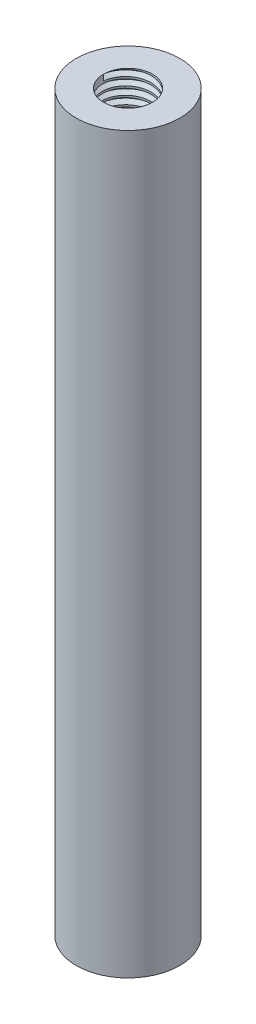
SolidWorks part; units mm, degrees
ref_plane "Front Plane" through (0, 0, 0) normal (0, 0, 1) x (1, 0, 0)
ref_plane "Top Plane" through (0, 0, 0) normal (0, 1, 0) x (1, 0, 0)
ref_plane "Right Plane" through (0, 0, 0) normal (1, 0, 0) x (0, 0, -1)
sketch "Sketch1" plane through (0, 0, 0) normal (0, 1, 0) x (1, 0, 0)
  circle A0 centre (0, 0) radius 6.35
extrude "Boss-Extrude1" add sketch "Sketch1" along normal blind 90
sketch "Sketch2" plane through (0, 90, 0) normal (0, 1, 0) x (1, 0, 0)
  point P0 (0, 0)
sketch "Sketch3" plane through (0, 0, 0) normal (0, -1, 0) x (-1, 0, 0)
  point P0 (0, 0)
hole_wizard "Tap Drill for M7x1.0 Tap1" positions "Sketch4" profile "Sketch5" hole size "M7x1.0" standard "ANSI Metric"
sketch "Sketch4" plane through (0, 90, 0) normal (0, 1, 0) x (1, 0, 0)
  point P0 (0, 0)
sketch "Sketch5" plane through (0, 90, 0) normal (1, 0, 0) x (0, 0, 1)
  line L0 (0, 0) -> (0, 27.2026)
  line L1 (0, 27.2026) -> (3, 25.4)
  line L2 (3, 25.4) -> (3, 0)
  line L5 (3, 0) -> (0, 0)
  line L10 (0, 27.2026) -> (-3, 25.4) construction
  line L11 (0, -6.35) -> (0, 107.95) construction
  dimension "Hole Dia." = 6
  dimension "Hole Depth" = 25.4
  dimension "Drill Angle" = 118
thread "Thread1" pitch 1 start angle 0, offset 0, length 0, pitch 1, diameter 6
ref_plane "Plane1" through (-3, 90, 0) normal (0, 0, 1) x (-1, 0, 0)
sketch "Thread Profile1" plane through (-3, 90, 0) normal (0, 0, 1) x (-1, 0, 0)
  line L0 (0, 0) -> (0, 1) construction
  line L1 (0, 0) -> (0.5413, 0.3125)
  line L2 (0.5413, 0.3125) -> (0.5413, 0.4375)
  line L3 (0.5413, 0.4375) -> (0, 0.75)
  line L4 (0.5413, 0.375) -> (0, 0.375) construction
  line L11 (0, 0) -> (0, 0.75)
  point P2 (0, 0)
  dimension "Pitch" = 1
  dimension "Profile_Angle" = 60
  dimension "Profile_Land" = 0.125
  dimension "Profile_Height" = 0.5413
hole_wizard "Tap Drill for 1/4-20 Tap1" positions "Sketch10" profile "Sketch11" hole size "1/4-20" standard "ANSI Inch"
sketch "Sketch10" plane through (0, 0, 0) normal (0, -1, 0) x (-1, 0, 0)
  point P0 (0, 0)
sketch "Sketch11" plane through (0, 0, 0) normal (1, 0, 0) x (0, 0, -1)
  line L0 (0, 0) -> (0, 26.9338)
  line L1 (0, 26.9338) -> (2.5527, 25.4)
  line L2 (2.5527, 25.4) -> (2.5527, 0)
  line L5 (2.5527, 0) -> (0, 0)
  line L10 (0, 26.9338) -> (-2.5527, 25.4) construction
  line L11 (0, -6.35) -> (0, 107.95) construction
  dimension "Hole Dia." = 5.1054
  dimension "Hole Depth" = 25.4
  dimension "Drill Angle" = 118
thread "Thread2" pitch 1.27 profile "Thread Profile2" start angle 0, offset 0, length 0, pitch 1.27, diameter 5.1054
ref_plane "Plane2" through (2.5527, 0, 0) normal (0, 0, 1) x (1, 0, 0)
sketch "Thread Profile2" plane through (2.5527, 0, 0) normal (0, 0, 1) x (1, 0, 0)
  line L0 (0, 0) -> (0, 1.27) construction
  line L1 (0, 0) -> (0.6874, 0.3969)
  line L2 (0.6874, 0.3969) -> (0.6874, 0.5556)
  line L3 (0.6874, 0.5556) -> (0, 0.9525)
  line L4 (0.6874, 0.4762) -> (0, 0.4762) construction
  line L11 (0, 0) -> (0, 0.9525)
  point P2 (0, 0)
  dimension "Pitch" = 1.27
  dimension "Profile_Angle" = 60
  dimension "Profile_Land" = 0.1588
  dimension "Profile_Height" = 0.6874
